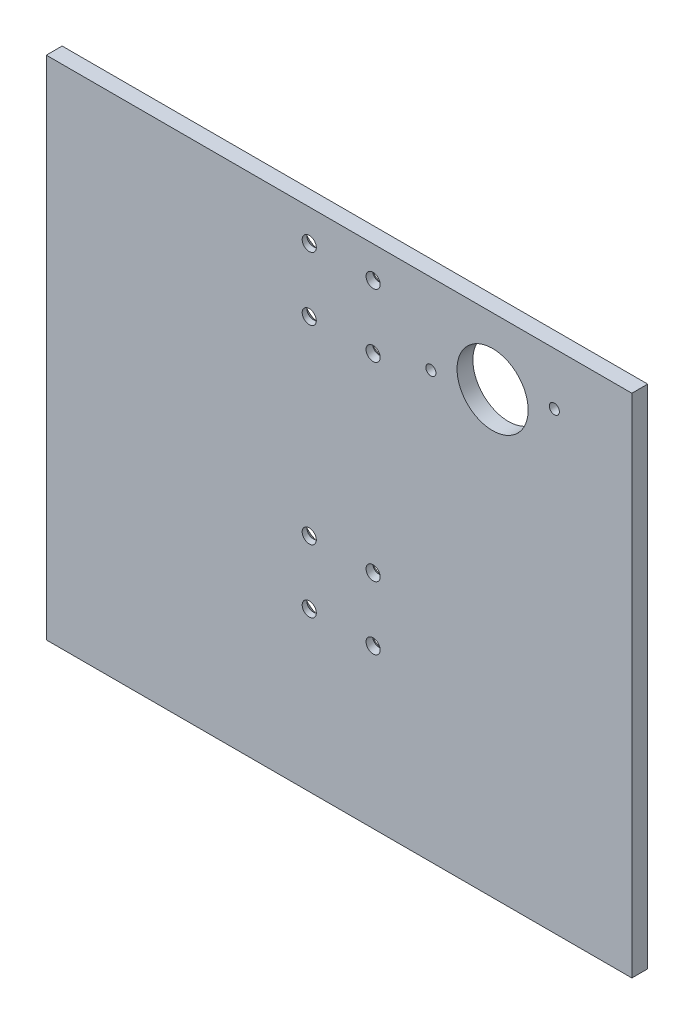
SolidWorks part; units mm, degrees
material "PC High Viscosity"
ref_plane "Front Plane" through (0, 0, 0) normal (0, 0, 1) x (1, 0, 0)
ref_plane "Top Plane" through (0, 0, 0) normal (0, 1, 0) x (1, 0, 0)
ref_plane "Right Plane" through (0, 0, 0) normal (1, 0, 0) x (0, 0, -1)
sketch "Sketch1" plane through (0, 0, 0) normal (0, 0, 1) x (1, 0, 0)
  line L1 (-117.475, -101.6) -> (117.475, -101.6)
  line L2 (-117.475, -101.6) -> (-117.475, 101.6)
  line L3 (-117.475, 101.6) -> (117.475, 101.6)
  line L4 (117.475, -101.6) -> (117.475, 101.6)
  line L5 (-117.475, -101.6) -> (117.475, 101.6) construction
  line L6 (-117.475, 101.6) -> (117.475, -101.6) construction
  point P0 (0, 0)
  dimension "D1" = 234.95
  dimension "D2" = 203.2
extrude "Boss-Extrude1" add sketch "Sketch1" along normal blind 6.35
sketch "Sketch2" plane through (0, 0, 6.35) normal (0, 0, 1) x (1, 0, 0)
  line L0 (117.475, 101.6) -> (-117.475, 101.6) construction
  line L1 (117.475, -101.6) -> (117.475, 101.6) construction
  circle A0 centre (61.595, 74.93) radius 14.2748
  dimension "D3" = 28.5496
  dimension "D1" = 26.67
  dimension "D2" = 55.88
extrude "Cut-Extrude1" cut sketch "Sketch2" against normal through all
hole_wizard "CSK for #10 Flat Head Machine Screw (100)1" positions "Sketch3" profile "Sketch4" countersink size "#10" standard "ANSI Inch" end condition through all
sketch "Sketch3" plane through (292.077, -265.5951, -43.8004) normal (0.1349, 0, 0.9909) x (0.9909, 0, -0.1349)
  point P0 (-308.0419, 227.4951)
  point P2 (-308.0419, 252.8951)
  point P4 (-308.042, 329.0951)
  point P6 (-308.042, 354.4951)
sketch "Sketch4" plane through (-13.1497, -38.1, -2.2498) normal (0, 1, 0) x (-0.9909, 0, 0.1349)
  line L0 (0, 0) -> (0, 26.1406)
  line L1 (0, 26.1406) -> (2.8067, 26.1406)
  line L2 (2.8067, 26.1406) -> (2.8067, 6.0833)
  line L3 (2.8067, 6.0833) -> (8.89, 0)
  line L4 (8.89, 0) -> (0, 0)
  line L5 (-2.8067, 6.0833) -> (-8.89, 0) construction
  line L6 (0, -6.35) -> (0, 107.95) construction
  dimension "Thru Hole Dia." = 5.6134
  dimension "Thru Hole Depth" = 26.1406
  dimension "Near C'Sink Dia." = 17.78
  dimension "Near C'Sink Angle" = 90
hole_wizard "CSK for #10 Flat Head Machine Screw (100)2" positions "Sketch5" profile "Sketch6" countersink size "#10" standard "ANSI Inch" end condition through all
sketch "Sketch5" plane through (292.4196, -265.5951, -41.2836) normal (0.1349, 0, 0.9909) x (0.9909, 0, -0.1349)
  point P0 (-282.6419, 227.4951)
  point P2 (-282.6419, 252.8951)
  point P4 (-282.642, 329.0951)
  point P6 (-282.642, 354.4951)
sketch "Sketch6" plane through (12.3608, -38.1, -3.1591) normal (0, 1, 0) x (-0.9909, 0, 0.1349)
  line L0 (0, 0) -> (0, 23.6006)
  line L1 (0, 23.6006) -> (2.8067, 23.6006)
  line L2 (2.8067, 23.6006) -> (2.8067, 6.0833)
  line L3 (2.8067, 6.0833) -> (8.89, 0)
  line L4 (8.89, 0) -> (0, 0)
  line L5 (-2.8067, 6.0833) -> (-8.89, 0) construction
  line L6 (0, -6.35) -> (0, 107.95) construction
  dimension "Thru Hole Dia." = 5.6134
  dimension "Thru Hole Depth" = 23.6006
  dimension "Near C'Sink Dia." = 17.78
  dimension "Near C'Sink Angle" = 90
sketch "Sketch10" plane through (0, 0, 0) normal (0, 0, -1) x (-1, 0, 0)
  line L0 (-117.475, -101.6) -> (-117.475, 101.6) construction
  line L1 (-117.475, 101.6) -> (117.475, 101.6) construction
  arc A0 (-85.9053, 82.5619) -> (-86.8058, 78.625) centre (-86.3556, 80.5935) ccw construction
  arc A1 (-86.8058, 78.625) -> (-85.9053, 82.5619) centre (-86.3556, 80.5935) ccw construction
  arc A2 (-36.3842, 71.235) -> (-37.2847, 67.2981) centre (-36.8344, 69.2665) ccw construction
  arc A3 (-37.2847, 67.2981) -> (-36.3842, 71.235) centre (-36.8344, 69.2665) ccw construction
  arc A4 (-85.9053, 82.5619) -> (-86.8058, 78.625) centre (-86.3556, 80.5935) ccw
  arc A5 (-86.8058, 78.625) -> (-85.9053, 82.5619) centre (-86.3556, 80.5935) ccw
  arc A6 (-36.3842, 71.235) -> (-37.2847, 67.2981) centre (-36.8344, 69.2665) ccw
  arc A7 (-37.2847, 67.2981) -> (-36.3842, 71.235) centre (-36.8344, 69.2665) ccw
  dimension "D1" = 31.1194
  dimension "D2" = 80.6406
  dimension "D3" = 21.0065
extrude "Cut-Extrude2" cut sketch "Sketch10" against normal through all
